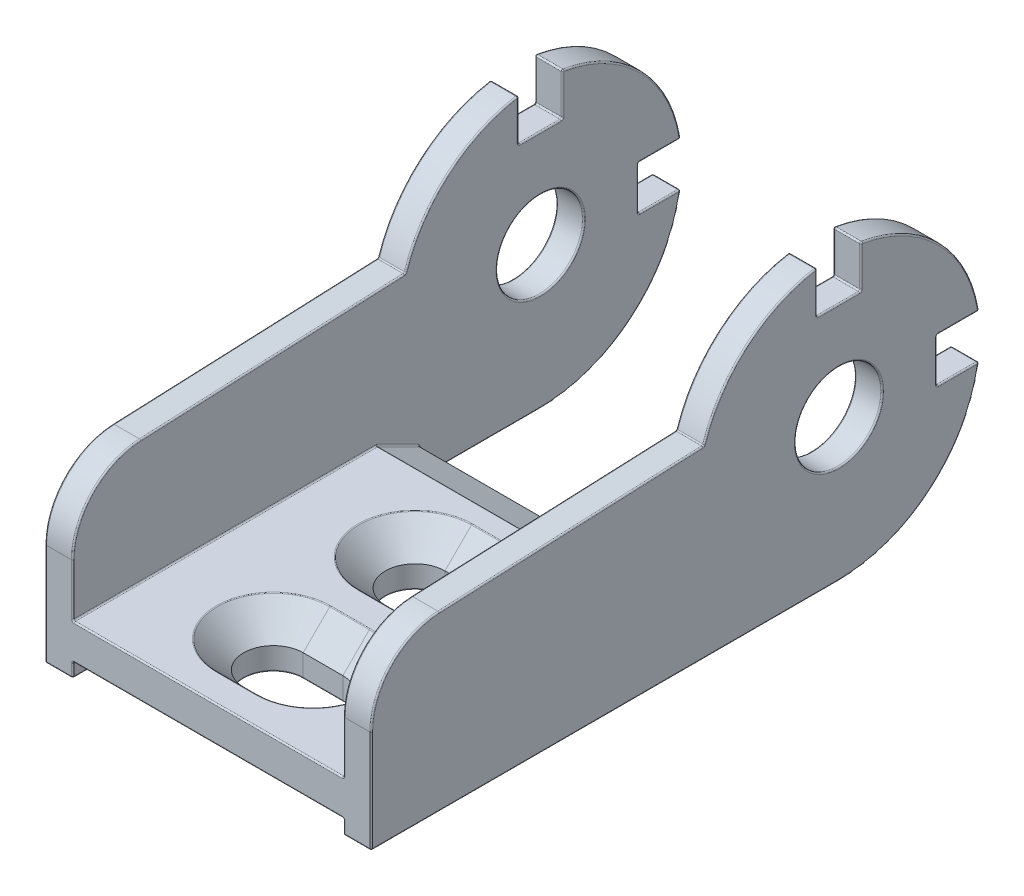
SolidWorks part; units mm, degrees
material "ABS PC"
ref_plane "Front Plane" through (0, 0, 0) normal (0, 0, 1) x (1, 0, 0)
ref_plane "Top Plane" through (0, 0, 0) normal (0, 1, 0) x (1, 0, 0)
ref_plane "Right Plane" through (0, 0, 0) normal (1, 0, 0) x (0, 0, -1)
sketch "Profile Sketch" plane through (0, 0, 0) normal (0, 0, 1) x (1, 0, 0)
  line L0 (-11.5, -10) -> (11.5, -10)
  line L1 (11.5, -10) -> (11.5, 10)
  line L2 (11.5, 10) -> (9.55, 10)
  line L3 (9.55, 10) -> (9.55, -6.5)
  line L4 (9.55, -6.5) -> (-9.55, -6.5)
  line L5 (-9.55, -6.5) -> (-9.55, 10)
  line L6 (-9.55, 10) -> (-11.5, 10)
  line L7 (-11.5, 10) -> (-11.5, -10)
  point P3 (0, -10)
  dimension "D1" = 3.5
  dimension "Ba" = 23
  dimension "D2" = 10
  dimension "Ha" = 20
  dimension "Bi" = 19.1
extrude "Body" add sketch "Profile Sketch" along normal blind 33 and the other way blind 10
sketch "Pivot Hole Sketch" plane through (0, 0, 0) normal (1, 0, 0) x (0, 0, -1)
  line L0 (10, -10) -> (10, 10) construction
  circle A0 centre (0, 0) radius 3.05
  point P5 (10, 0)
  dimension "D1" = 6.1
extrude "Pivot Hole" cut sketch "Pivot Hole Sketch" against normal through all both and the other way through all
sketch "Outside Shape Cut Out Sketch" plane through (0, 0, 0) normal (1, 0, 0) x (0, 0, -1)
  line L0 (10, -10) -> (10, 10) construction
  line L1 (10, -10) -> (-33, -10) construction
  line L2 (-28.2129, 2.204) -> (-9.5394, 3)
  line L3 (-33, -2.7914) -> (-33, -10)
  line L4 (-33, -10) -> (0, -10)
  line L5 (-33, -10) -> (-33, 10) construction
  line L6 (9.8791, -1.55) -> (6.9, -1.55)
  line L7 (6.9, -1.55) -> (6.9, 1.55)
  line L8 (6.9, 1.55) -> (9.8791, 1.55)
  line L9 (1.55, 9.8791) -> (1.55, 6.9)
  line L10 (1.55, 6.9) -> (-1.55, 6.9)
  line L11 (-1.55, 6.9) -> (-1.55, 9.8791)
  line L12 (6.9, -1.55) -> (0, -1.55) construction
  line L13 (6.9, 1.55) -> (0, 1.55) construction
  line L14 (0, -1.55) -> (0, 1.55) construction
  line L15 (1.55, 6.9) -> (1.55, 0) construction
  line L16 (1.55, 0) -> (-1.55, 0) construction
  line L17 (-1.55, 0) -> (-1.55, 6.9) construction
  line L18 (-35, 10) -> (10, 10)
  line L19 (-35, 10) -> (-35, -12)
  line L20 (-35, -12) -> (10, -12)
  line L21 (10, 10) -> (10, -12)
  line L22 (-35, 10) -> (10, -12) construction
  line L23 (-35, -12) -> (10, 10) construction
  line L24 (10, 10) -> (-33, 10) construction
  arc A0 (0, -10) -> (9.8791, -1.55) centre (0, 0) ccw
  arc A1 (-1.55, 9.8791) -> (-9.5394, 3) centre (0, 0) ccw
  arc A2 (9.8791, 1.55) -> (1.55, 9.8791) centre (0, 0) ccw
  arc A3 (-28.2129, 2.204) -> (-33, -2.7914) centre (-28, -2.7914) ccw
  point P16 (0, 0)
  point P23 (0, 0)
  point P28 (-33, 2)
  point P29 (-12.5, -1)
  dimension "D5" = 5
  dimension "D1" = 12
  dimension "D2" = 13
  dimension "D3" = 3.1
  dimension "D4" = 6.9
  dimension "D6" = 2
  dimension "D7" = 2
extrude "Outside Shape Cut Out" cut sketch "Outside Shape Cut Out Sketch" against normal through all both and the other way through all
sketch "Inside Shape Cut Out Sketch" plane through (0, 0, 0) normal (1, 0, 0) x (0, 0, -1)
  line L0 (-30, -8) -> (-30, -10)
  line L1 (-30, -10) -> (-33, -10)
  line L2 (-33, -10) -> (-33, -9)
  line L3 (-33, -9) -> (-31.5, -9)
  line L4 (-31.5, -9) -> (-31.5, -8)
  line L5 (-31.5, -8) -> (-30, -8)
  line L6 (0, -10) -> (-33, -10) construction
  line L7 (-33, -10) -> (-33, -2.7914) construction
  line L8 (-11.6, -6.5) -> (-8.6, -8)
  line L9 (-8.6, -8) -> (-8.6, -10)
  line L10 (-8.6, -10) -> (7.5993, -10)
  line L11 (7.5993, -10) -> (7.5993, -6.5)
  line L12 (7.5993, -6.5) -> (-11.6, -6.5)
  line L13 (7.5993, -6.5) -> (-33, -6.5) construction
  point P6 (-31.5, -10)
  point P7 (-30, -9)
  dimension "D1" = 3
  dimension "D2" = 2
  dimension "D3" = 2
  dimension "D4" = 3
  dimension "D5" = 24.4
extrude "Inside Shape Cut Out" cut sketch "Inside Shape Cut Out Sketch" against normal mid plane 19.1
sketch "Lightening Sketch" plane through (0, -10, 0) normal (0, 1, 0) x (1, 0, 0)
  line L0 (-9.55, -8.6) -> (9.55, -8.6) construction
  line L1 (-4, -19.6) -> (4, -19.6)
  line L2 (-4, -19.6) -> (-4, -23.6)
  line L3 (-4, -23.6) -> (4, -23.6)
  line L4 (4, -19.6) -> (4, -23.6)
  line L5 (-4, -19.6) -> (4, -23.6) construction
  line L6 (-4, -23.6) -> (4, -19.6) construction
  point P0 (0, -21.6)
  dimension "D1" = 8
  dimension "D2" = 4
  dimension "D3" = 11
extrude "Lightening" cut sketch "Lightening Sketch" along normal blind 0.5
hole_wizard "M4 4.2x7" positions "Sketch2" profile "Sketch3" size "M4" standard "ISO" slot yes end condition through all
sketch "Sketch2" plane through (0, -6.5, 0) normal (0, 1, 0) x (1, 0, 0)
  line L0 (-3.5, -27) -> (3.5, -27) construction
  line L1 (9.55, -33) -> (-9.55, -33) construction
  point P0 (0, -27)
  point P4 (0, -17)
  point P9 (0, -33)
  dimension "D1" = 7
  dimension "E" = 6
  dimension "A" = 10
sketch "Sketch3" plane through (0, -6.5, 27) normal (1, 0, 0) x (0, 0, 1)
  line L0 (0, 0) -> (0, 3.5)
  line L1 (0, 3.5) -> (2.1, 3.5)
  line L2 (2.1, 3.5) -> (2.1, 1.9)
  line L3 (2.1, 1.9) -> (4, 0)
  line L5 (4, 0) -> (0, 0)
  line L6 (-2.1, 1.9) -> (-4, 0) construction
  line L11 (0, -6.35) -> (0, 107.95) construction
  dimension "Thru Hole Dia." = 4.2
  dimension "Thru Hole Depth" = 3.5
  dimension "Near C'Sink Dia." = 8
  dimension "Near C'Sink Angle" = 90
sketch "15.15.BF.1PZ" plane through (-11.5, 0, 0) normal (-1, 0, 0) x (0, 0, 1)
  line L0 (31.5, -9) -> (15.5, -9) construction
  line L1 (0, -10) -> (33, -10) construction
  line L2 (33, -2.7914) -> (33, -10) construction
  text T0 "15.15.BF.И.1PZ" font "Arial Narrow" height 2
  dimension "D1" = 16
  dimension "D2" = 1
  dimension "D3" = 1.5
extrude "Text" add sketch "15.15.BF.1PZ" along normal blind 0.05
fillet "Production Fillet" radius 0.1 127 edges at (9.55, 8.3896, 1.55) (9.55, 8.3896, -1.55) (11.5, 8.3896, -1.55) (11.5, 8.3896, 1.55) (-9.55, 8.3896, -1.55) (-9.55, 8.3896, 1.55) (-11.5, 8.3896, 1.55) (-11.5, 8.3896, -1.55) (9.55, 1.55, -8.3896) (9.55, -1.55, -8.3896) (11.5, -1.55, -8.3896) (11.5, 1.55, -8.3896) (-9.55, -1.55, -8.3896) (-9.55, 1.55, -8.3896) (-11.5, 1.55, -8.3896) (-11.5, -1.55, -8.3896) (-9.55, -8.5, 31.5) (9.55, -8.5, 31.5) (9.55, -7.25, 10.1) (-9.55, -7.25, 10.1) (-9.55, 0.668, 31.61) (-11.5, 0.668, 31.61) (9.55, 0.668, 31.61) (11.5, 0.668, 31.61) (9.55, 7.578, 6.5249) (10.525, 9.8791, 1.55) (11.5, 7.578, 6.5249) (-9.55, 7.578, 6.5249) (-11.5, 7.578, 6.5249) (-10.525, 9.8791, 1.55) (9.55, 6.9, 0) (10.525, 6.9, -1.55) (11.5, 6.9, 0) (10.525, 6.9, 1.55) (-9.55, 6.9, 0) (-10.525, 6.9, 1.55) (-11.5, 6.9, 0) (-10.525, 6.9, -1.55) (-9.55, 7.0711, -7.0711) (-10.525, 9.8791, -1.55) (-11.5, 7.0711, -7.0711) (-10.525, 1.55, -9.8791) (9.55, 7.0711, -7.0711) (10.525, 1.55, -9.8791) (11.5, 7.0711, -7.0711) (10.525, 9.8791, -1.55) (11.5, -7.5993, -6.5) (10.525, -1.55, -9.8791) (9.55, -7.5993, -6.5) (-10.525, -1.55, -9.8791) (-11.5, -7.5993, -6.5) (-9.55, -7.5993, -6.5) (9.55, 0, -6.9) (10.525, -1.55, -6.9) (11.5, 0, -6.9) (10.525, 1.55, -6.9) (-9.55, 0, -6.9) (-10.525, 1.55, -6.9) (-11.5, 0, -6.9) (-10.525, -1.55, -6.9) (-4, -10, 21.6) (0, -10, 19.6) (4, -10, 21.6) (0, -10, 23.6) (9.55, -10, 31.5) (11.5, -10, 16.5) (9.55, -10, 4.3) (-9.55, -10, 4.3) (-11.5, -10, 16.5) (-9.55, -10, 31.5) (0, -10, 19.1) (-3.5, -10, 17) (0, -10, 14.9) (3.5, -10, 17) (3.5, -10, 27) (0, -10, 29.1) (-3.5, -10, 27) (0, -10, 24.9) (0, -9.5, 19.6) (-4, -9.5, 21.6) (0, -9.5, 23.6) (4, -9.5, 21.6) (0, -9, 31.5) (-9.55, -9, 32.25) (9.55, -9, 32.25) (0, -10, 30) (-9.55, -9, 30) (9.55, -9, 30) (0, -8, 30) (-9.55, -8, 30.75) (0, -8, 31.5) (9.55, -8, 30.75) (11.5, 0, -3.05) (9.55, 0, 3.05) (-11.5, 0, -3.05) (-9.55, 0, -3.05) (0, -8, 8.6) (-9.55, -9, 8.6) (0, -10, 8.6) (9.55, -9, 8.6) (0, -6.5, 31) (5.4, -6.5, 27) (0, -6.5, 23) (-5.4, -6.5, 27) (0, -6.5, 21) (5.4, -6.5, 17) (0, -6.5, 13) (-5.4, -6.5, 17) (9.55, -6.5, 22.3) (-9.55, -6.5, 22.3) (0, -6.5, 11.6) (-10.525, -10, 33) (-11.5, -6.3957, 33) (-9.55, -4.6457, 33) (0, -6.5, 33) (9.55, -4.6457, 33) (11.5, -6.3957, 33) (10.525, -10, 33) (9.55, -9.5, 33) (0, -9, 33) (-9.55, -9.5, 33) (-9.55, 2.602, 18.8762) (-11.5, 2.602, 18.8762) (-10.525, 3, 9.5394) (9.55, 2.602, 18.8762) (10.525, 3, 9.5394) (11.5, 2.602, 18.8762)
